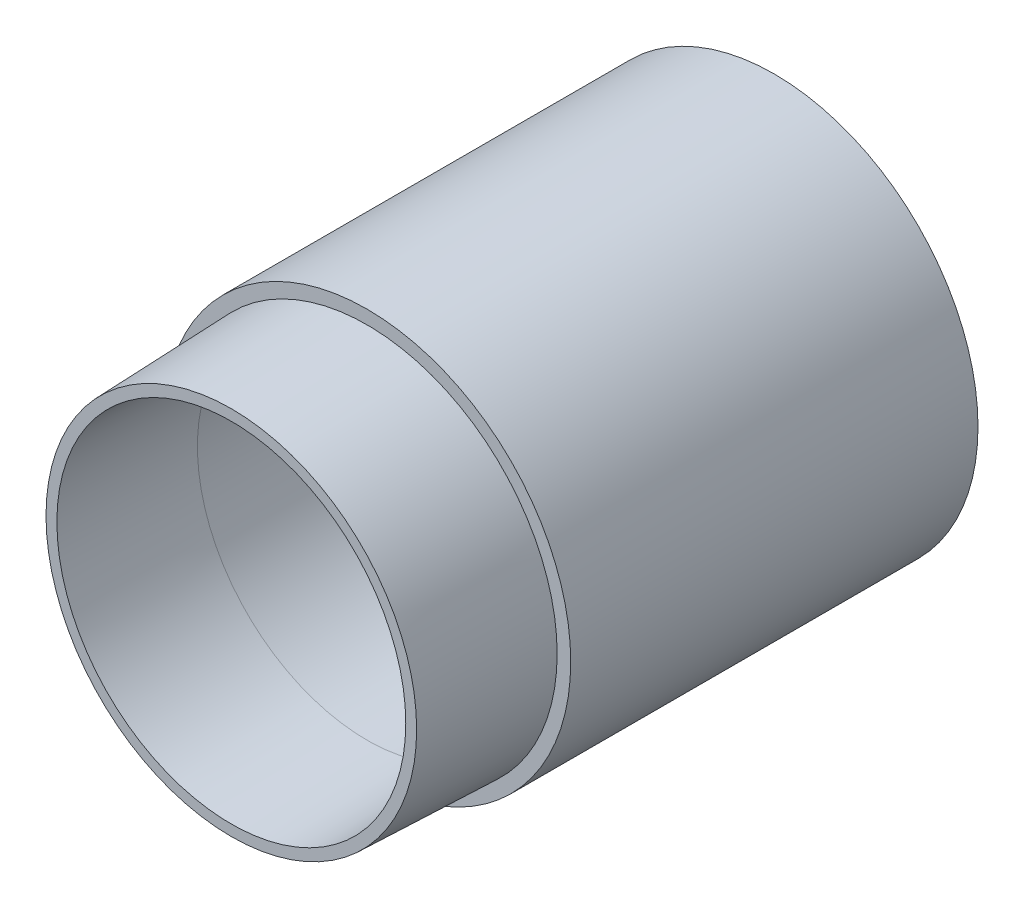
SolidWorks part; units mm, degrees
ref_plane "Alzado" through (0, 0, 0) normal (0, 0, 1) x (1, 0, 0)
ref_plane "Planta" through (0, 0, 0) normal (0, 1, 0) x (1, 0, 0)
ref_plane "Vista lateral" through (0, 0, 0) normal (1, 0, 0) x (0, 0, -1)
sketch "Croquis1" plane through (0, 0, 0) normal (0, 0, 1) x (1, 0, 0)
  circle A0 centre (0, 0) radius 15
  circle A1 centre (0, 0) radius 14
  dimension "D1" = 30
  dimension "D2" = 28
extrude "Saliente-Extruir1" add sketch "Croquis1" along normal blind 30
sketch "Croquis2" plane through (0, 0, 30) normal (0, 0, 1) x (1, 0, 0)
  circle A0 centre (0, 0) radius 14
  circle A1 centre (0, 0) radius 12.5
  dimension "D1" = 28
  dimension "D2" = 25
extrude "Saliente-Extruir2" add sketch "Croquis2" along normal blind 10 draft 2 and the other way blind 10
